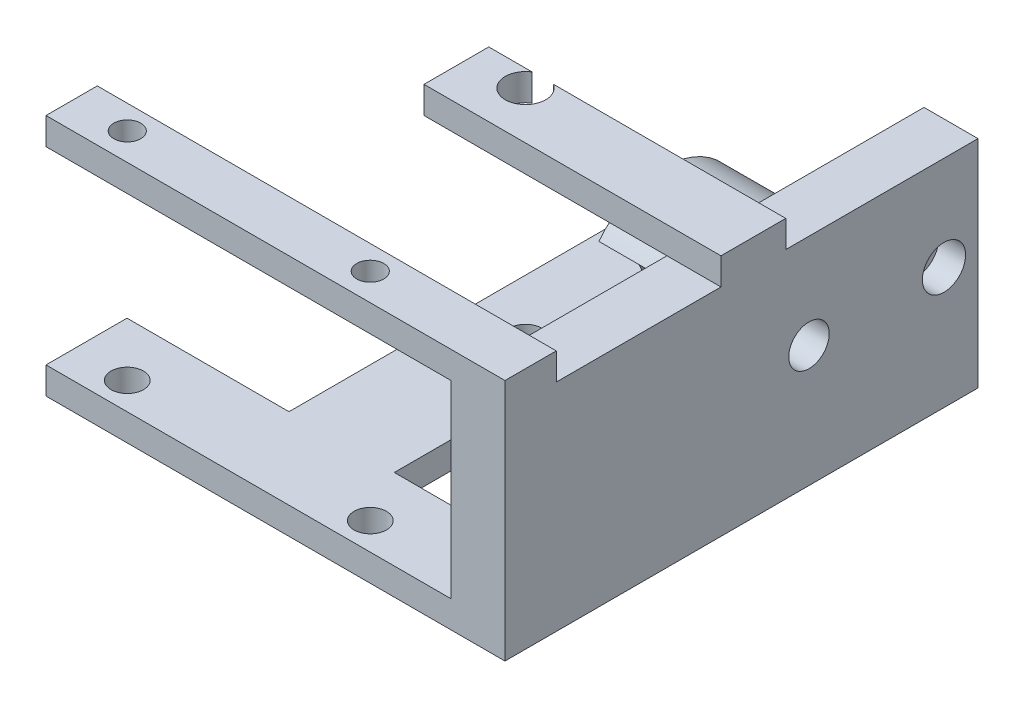
SolidWorks part; units mm, degrees
ref_plane "前视基准面" through (0, 0, 0) normal (0, 0, 1) x (1, 0, 0)
ref_plane "上视基准面" through (0, 0, 0) normal (0, 1, 0) x (1, 0, 0)
ref_plane "右视基准面" through (0, 0, 0) normal (1, 0, 0) x (0, 0, -1)
other "Configuration Table"
sketch "草图1" plane through (0, 0, 0) normal (1, 0, 0) x (0, 0, -1)
  line L9 (0, 0) -> (-15.52, 0)
  line L10 (0, 0) -> (0, -7)
  line L11 (0, -7) -> (-15.52, -7)
  line L12 (-15.52, 0) -> (-15.52, -7)
  circle A5 centre (-6.5, -3.5) radius 3.25
  circle A6 centre (-10.7, -3.5) radius 4
  circle A7 centre (-12.4205, 0) radius 1.5
  circle A8 centre (-12.4205, 0) radius 3.1
  circle A9 centre (-10.7, -3.5) radius 0.6
  circle A10 centre (-6.5, -3.5) radius 0.75
  circle A11 centre (-6.5, -3.5) radius 1.6
  point P12 (0, -3.5)
  dimension "D1" = 4.2
  dimension "D4" = 6.5
  dimension "D5" = 8
  dimension "D9" = 3
  dimension "D10" = 6.2
  dimension "D11" = 1.2
  dimension "D12" = 1.5
  dimension "D13" = 3.2
  dimension "D2" = 3.9
  dimension "D3" = 3.5
  dimension "D6" = 7
  dimension "D7" = 15.52
  dimension "D8" = 6.5
extrude "凸台-拉伸1" add sketch "草图1" along normal blind 2 contours L10 L11 L12 L9
sketch "草图2" plane through (2, 0, 0) normal (1, 0, 0) x (0, 0, -1)
  line L0 (0, 0) -> (0, -7) construction
  line L1 (0, 0) -> (1, 0)
  line L2 (0, 0) -> (0, -7)
  line L3 (0, -7) -> (1, -7)
  line L4 (1, 0) -> (1, -7)
  line L5 (0, 0) -> (-15.52, 0) construction
  line L6 (-15.52, 0) -> (-16.52, 0)
  line L7 (-15.52, 0) -> (-15.52, -7)
  line L8 (-15.52, -7) -> (-16.52, -7)
  line L9 (-16.52, 0) -> (-16.52, -7)
  line L10 (-15.52, 0) -> (-15.52, -7) construction
  line L12 (0, -7) -> (-15.52, -7) construction
  circle A0 centre (-13.26, -3.5) radius 0.6
  circle A1 centre (-9.26, -4.7806) radius 0.6
  circle A2 centre (-5.26, -3.5) radius 0.75
  circle A3 centre (-13.26, -3.5) radius 2
  circle A4 centre (-9.26, -4.7806) radius 2
  circle A5 centre (-5.26, -3.5) radius 3
  circle A6 centre (-9.26, -4.7806) radius 3
  circle A7 centre (-13.26, -3.5) radius 3
  circle A8 centre (-11.5395, 0) radius 1.25
  circle A9 centre (-13.26, -3.5) radius 3.5
  dimension "D1" = 1.2
  dimension "D2" = 1.5
  dimension "D4" = 4
  dimension "D5" = 6
  dimension "D6" = 2.5
  dimension "D7" = 7
  dimension "D3" = 1
extrude "切除-拉伸1" cut sketch "草图2" against normal through all contours A0 | A1 | A2
extrude "凸台-拉伸2" add sketch "草图2<2>" against normal through all contours L8 L9 L6 L7 | L3 L4 L1 L2
sketch "草图2<2>" plane through (2, 0, 0) normal (1, 0, 0) x (0, 0, -1) same geometry as "草图2"
extrude "凸台-拉伸3" add sketch "草图2<4>" against normal blind 1.7 from surface contours A7 A4 A5 A1 | A4 A5 | A2 A6 A5 A4 | A6 A2 A5 | A7 A4 A5 A6 region at (2, -2.3264, 9.0146) region at (2, -4.0821, 7.0782) region at (2, -0.668, 4.5586) region at (2, -2.8494, 9.0089) region at (2, -4.2978, 7.752) starting at face at (0, -3.5, 12.66)
sketch "草图2<4>" plane through (2, 0, 0) normal (1, 0, 0) x (0, 0, -1) same geometry as "草图2"
sketch "草图3" plane through (-1.7, 0, 0) normal (-1, 0, 0) x (0, 0, 1)
  circle A1 centre (9.26, -4.7806) radius 3.5
  circle A4 centre (9.26, -4.7806) radius 0.6 construction
  circle M3 centre (5.26, -3.5) radius 0.75
  arc M6 (7.9132, -2.0999) -> (7.4252, -5.5765) centre (5.26, -3.5) ccw
  dimension "D1" = 7
extrude "凸台-拉伸4" add sketch "草图3" along normal blind 1.7 from surface contours A1 M6 M3 region at (-1.7, -3.2641, 4.5231) starting at face at (-1.7, -4.7806, 8.66)
extrude "凸台-拉伸5" add sketch "草图2<5>" against normal blind 1 contours A0 | A1
sketch "草图2<5>" plane through (2, 0, 0) normal (1, 0, 0) x (0, 0, -1) same geometry as "草图2"
sketch "草图4" plane through (0, 0, 0) normal (0, 1, 0) x (1, 0, 0)
  line L0 (2, 1) -> (2, -16.52) construction
  line L1 (2, -6.12) -> (-9, -6.12)
  line L2 (2, -6.12) -> (2, -8.52)
  line L3 (2, -8.52) -> (-9, -8.52)
  line L4 (-9, -6.12) -> (-9, -8.52)
  line L5 (0, -16.52) -> (2, -16.52) construction
  line L6 (2, -14.62) -> (-15, -14.62)
  line L7 (2, -14.62) -> (2, -16.52)
  line L8 (2, -16.52) -> (-15, -16.52)
  line L9 (-15, -14.62) -> (-15, -16.52)
  circle A0 centre (-13, -15.51) radius 0.5
  circle A1 centre (-4, -15.51) radius 0.5
  circle A3 centre (-7, -6.76) radius 0.75
  point P18 (0, 0)
  point P19 (0, 0)
  point P20 (0, 0)
  line M1 (0, 1) -> (0, -16.52)
  line M3 (2, -16.52) -> (2, 1)
  dimension "D6" = 1.5
  dimension "D7" = 1
  dimension "D1" = 1.9
  dimension "D2" = 17
  dimension "D3" = 8
  dimension "D4" = 2.4
  dimension "D5" = 11
extrude "凸台-拉伸6" add sketch "草图4" along normal blind 1 contours A3 L1 L4 L3 M1 | L3 L1 M3 M1 | L9 L8 L7 L6 | A0 | A1 region at (1, 0, 7.32) region at (-4.2852, 0, 7.3661)
sketch "草图5" plane through (0, -7, 0) normal (0, -1, 0) x (1, 0, 0)
  line L0 (0, 16.52) -> (2, 16.52) construction
  line L1 (2, 16.52) -> (-15, 16.52)
  line L2 (2, 16.52) -> (2, 13.52)
  line L3 (2, 13.52) -> (-15, 13.52)
  line L4 (-15, 16.52) -> (-15, 13.52)
  line L5 (0, -1) -> (2, -1) construction
  line L6 (2, -1) -> (-9, -1)
  line L7 (2, -1) -> (2, 1)
  line L8 (2, 1) -> (-9, 1)
  line L9 (-9, -1) -> (-9, 1)
  line L10 (2, -1) -> (2, 16.52) construction
  line L12 (-5.1, 13.52) -> (-9, 13.52)
  line L13 (-5.1, 13.52) -> (-5.1, -1)
  line L14 (-5.1, -1) -> (-9, -1)
  line L15 (-9, 13.52) -> (-9, -1)
  line L16 (2, 13.52) -> (-1.7, 13.52)
  line L17 (2, 13.52) -> (2, 1)
  line L18 (2, 1) -> (-1.7, 1)
  line L19 (-1.7, 13.52) -> (-1.7, 1)
  circle A0 centre (-13, 15.51) radius 0.6
  circle A1 centre (-4, 15.51) radius 0.6
  circle A2 centre (-4.5, -0.24) radius 0.6
  circle A3 centre (-7, 6.76) radius 0.6
  point P28 (0, 0)
  line M11 (0, 16.52) -> (0, -1)
  line M13 (2, -1) -> (2, 16.52)
  dimension "D1" = 1.2
  dimension "D2" = 1.2
  dimension "D3" = 17
  dimension "D4" = 3
  dimension "D5" = 2
  dimension "D6" = 3.7
  dimension "D7" = 7.1
  dimension "D8" = 3.9
extrude "凸台-拉伸7" add sketch "草图5" along normal blind 1 contours L8 L3 M13 M11 | L3 L19 L8 M11 | L6 L9 L8 L7 | A2 | L3 L4 L1 L2 | A0 | A1 | L13 L14 L15 L12 | A3 region at (1, -7, 7.26) region at (-0.85, -7, 7.26)
sketch "草图6" plane through (2, 0, 0) normal (1, 0, 0) x (0, 0, -1)
  circle A0 centre (-0.26, -3.5) radius 0.6
  circle A1 centre (-0.26, -3.5) radius 0.8
  dimension "D1" = 1.2
  dimension "D2" = 1.6
extrude "切除-拉伸2" cut sketch "草图6" against normal through all contours A0
extrude "切除-拉伸3" cut sketch "草图6<3>" against normal blind 1 contours A1
sketch "草图6<3>" plane through (2, 0, 0) normal (1, 0, 0) x (0, 0, -1) same geometry as "草图6"
